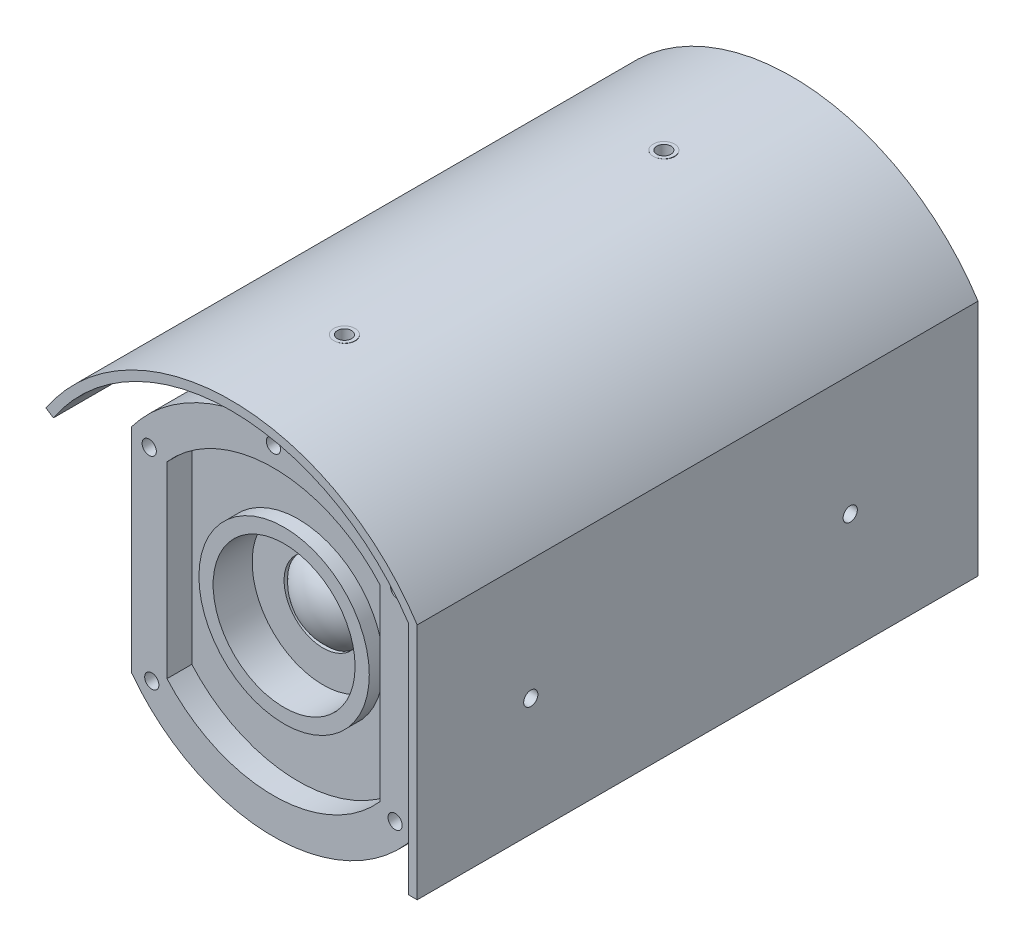
SolidWorks part; units mm, degrees
ref_plane "Front Plane" through (0, 0, 0) normal (0, 0, 1) x (1, 0, 0)
ref_plane "Top Plane" through (0, 0, 0) normal (0, 1, 0) x (1, 0, 0)
ref_plane "Right Plane" through (0, 0, 0) normal (1, 0, 0) x (0, 0, -1)
sketch "Sketch1" plane through (0, 0, 0) normal (0, 0, 1) x (1, 0, 0)
  line L2 (-40, -30) -> (-40, 30)
  line L3 (40, -30) -> (40, 30)
  line L5 (40, 0) -> (-40, 0) construction
  arc A0 (40, 30) -> (-40, 30) centre (0, 0) ccw
  arc A1 (40, -30) -> (-40, -30) centre (0, 0) cw
  point P18 (40, 0)
  point P19 (-40, 0)
  dimension "D1" = 60
  dimension "D2" = 80
extrude "Boss-Extrude1" add sketch "Sketch1" along normal blind 140
sketch "Sketch2" plane through (0, 0, 140) normal (0, 0, 1) x (1, 0, 0)
  line L4 (-30, 26.4575) -> (-30, -26.4575)
  line L5 (30, -26.4575) -> (30, 26.4575)
  line L6 (-30, 26.4575) -> (-30, -26.4575)
  line L7 (30, -26.4575) -> (30, 26.4575)
  arc A4 (30, 26.4575) -> (-30, 26.4575) centre (0, 0) ccw
  arc A5 (-30, -26.4575) -> (30, -26.4575) centre (0, 0) ccw
  arc A6 (30, 26.4575) -> (-30, 26.4575) centre (0, 0) ccw
  arc A7 (-30, -26.4575) -> (30, -26.4575) centre (0, 0) ccw
  dimension "D1" = 10
extrude "Cut-Extrude1" cut sketch "Sketch2" against normal blind 7
sketch "Sketch3" plane through (0, 0, 140) normal (0, 0, 1) x (1, 0, 0)
  line L2 (52.5, -33.1662) -> (52.5, 33.9116)
  line L3 (-50, 33.1662) -> (-52.0833, 34.5482)
  line L4 (-50, 33.1662) -> (-50, -33.1662)
  line L5 (50, -33.1662) -> (50, 33.1662)
  line L6 (52.5, -33.1662) -> (50, -33.1662)
  line L7 (50, -33.1662) -> (50, 33.1662)
  arc A2 (52.5, 33.9116) -> (-52.0833, 34.5482) centre (0, 0) ccw
  arc A4 (50, 33.1662) -> (-50, 33.1662) centre (0, 0) ccw
  arc A5 (-50, -33.1662) -> (50, -33.1662) centre (0, 0) ccw
  arc A6 (50, 33.1662) -> (-50, 33.1662) centre (0, 0) ccw
  dimension "D1" = 10
  dimension "D2" = 2.5
extrude "Boss-Extrude2" add sketch "Sketch3" along normal blind 12 and the other way blind 146 separate body
sketch "Sketch4" plane through (0, 0, 133) normal (0, 0, 1) x (1, 0, 0)
  circle A0 centre (0, 0) radius 20
  circle A1 centre (0, 0) radius 24
  dimension "D1" = 40
  dimension "D3" = 4
extrude "Boss-Extrude3" add sketch "Sketch4" along normal blind 4
sketch "Sketch5" plane through (0, 0, 133) normal (0, 0, 1) x (1, 0, 0)
  circle A1 centre (0, 0) radius 20
  circle A2 centre (0, 0) radius 20
  dimension "D1" = 0
extrude "Cut-Extrude2" cut sketch "Sketch5" against normal blind 7
sketch "Sketch6" plane through (0, 0, 126) normal (0, 0, 1) x (1, 0, 0)
  circle A0 centre (0, 0) radius 11
  dimension "D1" = 22
extrude "Cut-Extrude3" cut sketch "Sketch6" against normal blind 1
dome "Dome1" faces to dome 1 distance 5 reverse direction no elliptical dome no face at (11, 0, 125) parameters "D1"=5
sketch "Sketch7" plane through (52.5, 0, 0) normal (1, 0, 0) x (0, 0, -1)
  circle A0 centre (-120, 0) radius 3
  circle A1 centre (-30, 0) radius 3
  dimension "D3" = 6
  dimension "D1" = 90
  dimension "D2" = 30
extrude "Boss-Extrude4" add sketch "Sketch7" against normal up to surface (12.5 mm away) up to face at (40, 0, 70)
sketch "Sketch8" plane through (52.5, 0, 0) normal (1, 0, 0) x (0, 0, -1)
  circle A6 centre (-120, 0) radius 2
  circle A8 centre (-30, 0) radius 2
  dimension "D1" = 4
extrude "Cut-Extrude4" cut sketch "Sketch8" against normal blind 17
ref_plane "Plane1" through (0, 62.5, 0) normal (0, 1, 0) x (-1, 0, 0)
sketch "Sketch9" plane through (0, 62.5, 0) normal (0, 1, 0) x (-1, 0, 0)
  line L0 (-52.5, 120) -> (0, 120) construction
  line L1 (-52.5, 123) -> (-52.5, 117) construction
  circle A0 centre (0, 120) radius 3
  circle A1 centre (0, 30) radius 3
  dimension "D2" = 6
  dimension "D1" = 90
extrude "Boss-Extrude5" add sketch "Sketch9" against normal up to surface (12.5 mm away) up to face at (0, 40, 70)
sketch "Sketch10" plane through (0, 62.5, 0) normal (0, 1, 0) x (1, 0, 0)
  circle A0 centre (0, -30) radius 2
  circle A1 centre (0, -120) radius 2
  arc A2 (0, -123) -> (0, -117) centre (0, -120) ccw construction
  dimension "D1" = 4
extrude "Cut-Extrude5" cut sketch "Sketch10" against normal blind 17
sketch "Sketch11" plane through (0, 0, 0) normal (0, 0, -1) x (-1, 0, 0)
  line L4 (-42, 30.6594) -> (-42, -30.6594)
  line L5 (42, -30.6594) -> (42, 30.6594)
  line L6 (-42, 30.6594) -> (-42, -30.6594)
  line L7 (42, -30.6594) -> (42, 30.6594)
  line L8 (-40, 30) -> (-40, -30)
  line L9 (40, -30) -> (40, 30)
  line L10 (-40, 30) -> (-40, -30)
  line L11 (40, -30) -> (40, 30)
  arc A4 (42, 30.6594) -> (-42, 30.6594) centre (0, 0) ccw
  arc A5 (-42, -30.6594) -> (42, -30.6594) centre (0, 0) ccw
  arc A6 (42, 30.6594) -> (-42, 30.6594) centre (0, 0) ccw
  arc A7 (-42, -30.6594) -> (42, -30.6594) centre (0, 0) ccw
  arc A8 (40, 30) -> (-40, 30) centre (0, 0) ccw
  arc A9 (-40, -30) -> (40, -30) centre (0, 0) ccw
  arc A10 (40, 30) -> (-40, 30) centre (0, 0) ccw
  arc A11 (-40, -30) -> (40, -30) centre (0, 0) ccw
  dimension "D1" = 2
  dimension "D2" = 0
extrude "Boss-Extrude6" add sketch "Sketch11" against normal blind 7
sketch "Sketch12" plane through (0, 0, 0) normal (0, 0, -1) x (-1, 0, 0)
  line L0 (-35, -2.5) -> (35, -2.5)
  line L1 (-35, -6) -> (35, -6)
  line L2 (-35, -12) -> (35, -12)
  line L3 (-35, -8.5) -> (35, -8.5)
  line L4 (-35, 0) -> (35, 0)
  line L5 (-35, 3.5) -> (35, 3.5)
  line L6 (-35, 28.2843) -> (-35, -28.2843)
  line L7 (35, -28.2843) -> (35, 28.2843)
  line L8 (-35, 28.2843) -> (-35, -28.2843)
  line L9 (35, -28.2843) -> (35, 28.2843)
  line L10 (-35, 6) -> (35, 6)
  line L11 (-35, 9.5) -> (35, 9.5)
  line L12 (-35, 12) -> (35, 12)
  line L13 (-35, 15.5) -> (35, 15.5)
  line L14 (-35, 18) -> (35, 18)
  line L15 (-35, 21.5) -> (35, 21.5)
  line L16 (-35, 24) -> (35, 24)
  line L17 (-35, 27.5) -> (35, 27.5)
  line L18 (-33.541, 30) -> (33.541, 30)
  line L19 (-30.0458, 33.5) -> (30.0458, 33.5)
  line L20 (-27, 36) -> (27, 36)
  line L21 (-21.5581, 39.5) -> (21.5581, 39.5)
  line L22 (-16.1555, 42) -> (16.1555, 42)
  line L23 (-35, -18) -> (35, -18)
  line L24 (-35, -14.5) -> (35, -14.5)
  line L25 (-35, -24) -> (35, -24)
  line L26 (-35, -20.5) -> (35, -20.5)
  line L27 (-33.541, -30) -> (33.541, -30)
  line L28 (-35, -26.5) -> (35, -26.5)
  line L29 (-35, 45.5) -> (35, 45.5) [skipped]
  line L30 (-27, -36) -> (27, -36)
  line L31 (-31.1247, -32.5) -> (31.1247, -32.5)
  line L32 (-16.1555, -42) -> (16.1555, -42)
  line L33 (-23.297, -38.5) -> (23.297, -38.5)
  arc A7 (35, 28.2843) -> (-35, 28.2843) centre (0, 0) ccw
  arc A8 (-35, -28.2843) -> (35, -28.2843) centre (0, 0) ccw
  arc A9 (35, 28.2843) -> (-35, 28.2843) centre (0, 0) ccw
  arc A10 (-35, -28.2843) -> (35, -28.2843) centre (0, 0) ccw
  dimension "D2" = 3.5
  dimension "D4" = 2.5
  dimension "D5" = 3.5
  dimension "D1" = 7
  dimension "D3" = 8
  dimension "D6" = 7
extrude "Cut-Extrude6" cut sketch "Sketch12" against normal blind 5 contours L22 A9 | L20 A9 L21 | L18 A9 L19 | L17 L8 L16 L9 | L15 L8 L14 L9 | L13 L8 L12 L9 | L11 L8 L10 L9 | L4 L9 L5 L8 | L1 L9 L0 L8 | L2 L9 L3 L8 | L24 L8 L23 L9 | L26 L8 L25 L9 | L8 A10 L27 L9 L28 | L31 A10 L30 | L33 A10 L32 region at (0, -4.25, 0) region at (0, 1.75, 0) region at (0, -10.25, 0) region at (0, 7.75, 0) region at (0, -16.25, 0) region at (0, 13.75, 0) region at (0, -22.25, 0) region at (0, 19.75, 0) region at (0, -28.238, 0) region at (0, 25.75, 0) region at (0, -34.2088, 0) region at (0, 31.718, 0) region at (0, -40.1467, 0) region at (0, 37.6852, 0) region at (0, 43.2035, 0)
ref_plane "Plane2" through (-101.0147, 0, 0) normal (1, 0, 0) x (0, 0, -1)
sketch "Sketch16" plane through (0, 0, 140) normal (0, 0, 1) x (1, 0, 0)
  line L0 (2, 45.5) -> (-2, 45.5) construction
  circle A0 centre (35, 27.5) radius 2
  circle A1 centre (-35, 27.5) radius 2
  circle A2 centre (0, 45.5) radius 2
  circle A3 centre (34.2812, -29.1513) radius 2
  arc A4 (33.541, -30) -> (35, -28.2843) centre (0, 0) ccw construction
  circle A5 centre (-34.2812, -29.1513) radius 2
  arc A6 (-35, -28.2843) -> (-33.541, -30) centre (0, 0) ccw construction
  dimension "D1" = 4
extrude "Cut-Extrude8" cut sketch "Sketch16" against normal blind 5
scale "Ölçek1" bodies to scale 116 115 114 scale about centroid uniform scaling yes scale factor 0.1
